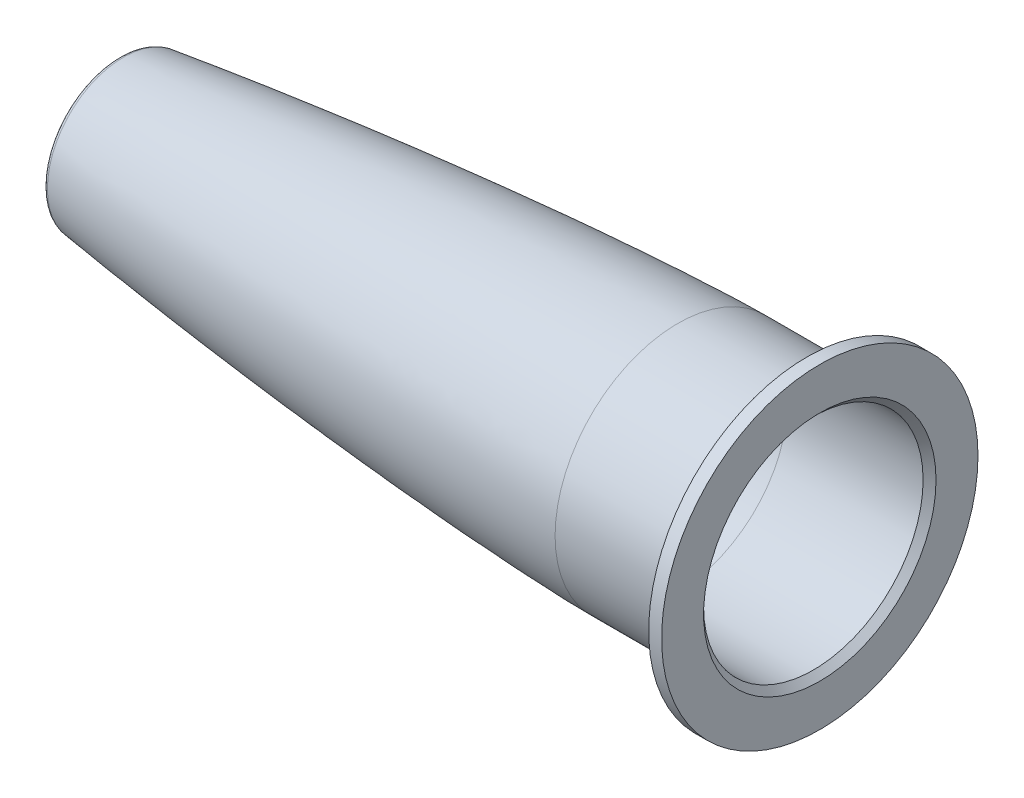
SolidWorks part; units mm, degrees
ref_plane "Front Plane" through (0, 0, 0) normal (0, 0, 1) x (1, 0, 0)
ref_plane "Top Plane" through (0, 0, 0) normal (0, 1, 0) x (1, 0, 0)
ref_plane "Right Plane" through (0, 0, 0) normal (1, 0, 0) x (0, 0, -1)
curve "Curve1"
  spline degree 3 poles (0, 0, 0) (0.3239, 0.2563, 0) (0.9404, 0.7441, 0) (1.9928, 1.2129, 0) (2.9928, 1.6503, 0) (3.9962, 2.0429, 0) (4.997, 2.4136, 0) (5.9977, 2.765, 0) (6.9982, 3.102, 0) (7.9985, 3.4266, 0) (8.9987, 3.7409, 0) (9.9989, 4.0463, 0) (10.999, 4.3437, 0) (11.9992, 4.6341, 0) (12.9993, 4.9182, 0) (13.9993, 5.1965, 0) (14.9994, 5.4695, 0) (15.9994, 5.7378, 0) (16.9995, 6.0015, 0) (17.9995, 6.261, 0) (18.9996, 6.5167, 0) (19.9996, 6.7687, 0) (20.9996, 7.0173, 0) (21.9996, 7.2626, 0) (22.9997, 7.5048, 0) (23.9997, 7.7441, 0) (24.9997, 7.9806, 0) (25.9997, 8.2145, 0) (26.9997, 8.4458, 0) (27.9997, 8.6747, 0) (28.9998, 8.9012, 0) (29.9998, 9.1256, 0) (30.9998, 9.3477, 0) (31.9998, 9.5678, 0) (32.9998, 9.7859, 0) (33.9998, 10.0021, 0) (34.9998, 10.2164, 0) (35.9998, 10.4289, 0) (36.9998, 10.6396, 0) (37.9998, 10.8486, 0) (38.9998, 11.056, 0) (39.9998, 11.2617, 0) (40.9999, 11.4659, 0) (41.9999, 11.6686, 0) (42.9999, 11.8698, 0) (43.9999, 12.0696, 0) (44.9999, 12.2679, 0) (45.9999, 12.4649, 0) (46.9999, 12.6605, 0) (47.9999, 12.8548, 0) (48.9999, 13.0478, 0) (49.9999, 13.2396, 0) (50.9999, 13.4301, 0) (51.9999, 13.6194, 0) (52.9999, 13.8076, 0) (53.9999, 13.9946, 0) (54.9999, 14.1804, 0) (55.9999, 14.3652, 0) (56.9999, 14.5488, 0) (57.9999, 14.7314, 0) (58.9999, 14.9129, 0) (59.9999, 15.0934, 0) (60.9999, 15.2728, 0) (61.9999, 15.4513, 0) (62.9999, 15.6288, 0) (63.9999, 15.8052, 0) (64.9999, 15.9808, 0) (65.9999, 16.1554, 0) (66.9999, 16.329, 0) (67.9999, 16.5018, 0) (68.9999, 16.6736, 0) (69.9999, 16.8445, 0) (70.9999, 17.0146, 0) (71.9999, 17.1838, 0) (72.9999, 17.3522, 0) (73.9999, 17.5197, 0) (74.9999, 17.6863, 0) (75.9999, 17.8522, 0) (76.9999, 18.0172, 0) (77.9999, 18.1814, 0) (78.9999, 18.3449, 0) (79.9999, 18.5075, 0) (80.9999, 18.6694, 0) (81.9999, 18.8305, 0) (82.9999, 18.9908, 0) (83.9999, 19.1504, 0) (84.9999, 19.3092, 0) (85.9999, 19.4673, 0) (86.9999, 19.6247, 0) (87.9999, 19.7814, 0) (88.9999, 19.9373, 0) (89.9999, 20.0925, 0) (90.9999, 20.2471, 0) (91.9999, 20.4009, 0) (92.9999, 20.554, 0) (93.9999, 20.7065, 0) (95, 20.8583, 0) (96, 21.0094, 0) (97, 21.1598, 0) (98, 21.3096, 0) (99, 21.4587, 0) (100, 21.6072, 0) (101, 21.755, 0) (102, 21.9022, 0) (103, 22.0488, 0) (104, 22.1947, 0) (105, 22.34, 0) (106, 22.4846, 0) (107, 22.6287, 0) (108, 22.7721, 0) (109, 22.915, 0) (110, 23.0572, 0) (111, 23.1988, 0) (112, 23.3398, 0) (113, 23.4803, 0) (114, 23.6201, 0) (115, 23.7594, 0) (116, 23.898, 0) (117, 24.0361, 0) (118, 24.1736, 0) (119, 24.3106, 0) (120, 24.4469, 0) (121, 24.5827, 0) (122, 24.718, 0) (123, 24.8526, 0) (124, 24.9867, 0) (125, 25.1203, 0) (126, 25.2533, 0) (127, 25.3857, 0) (128, 25.5176, 0) (129, 25.649, 0) (130, 25.7798, 0) (131, 25.91, 0) (132, 26.0397, 0) (133, 26.1689, 0) (134, 26.2975, 0) (135, 26.4257, 0) (136, 26.5532, 0) (137, 26.6803, 0) (138, 26.8068, 0) (139, 26.9328, 0) (140, 27.0582, 0) (141, 27.1832, 0) (142, 27.3076, 0) (143, 27.4315, 0) (144, 27.5549, 0) (145, 27.6777, 0) (146, 27.8001, 0) (147, 27.9219, 0) (148, 28.0432, 0) (149, 28.1641, 0) (150, 28.2844, 0) (151, 28.4041, 0) (152, 28.5234, 0) (153, 28.6422, 0) (154, 28.7605, 0) (155, 28.8782, 0) (156, 28.9955, 0) (157, 29.1122, 0) (158, 29.2285, 0) (159, 29.3442, 0) (160, 29.4595, 0) (161, 29.5742, 0) (162, 29.6885, 0) (163, 29.8022, 0) (164, 29.9155, 0) (165, 30.0282, 0) (166, 30.1405, 0) (167, 30.2522, 0) (168, 30.3635, 0) (169, 30.4743, 0) (170, 30.5845, 0) (171, 30.6943, 0) (172, 30.8036, 0) (173, 30.9124, 0) (174, 31.0207, 0) (175, 31.1285, 0) (176, 31.2358, 0) (177, 31.3426, 0) (178, 31.4489, 0) (179, 31.5547, 0) (180, 31.66, 0) (181, 31.7649, 0) (182, 31.8692, 0) (183, 31.973, 0) (184, 32.0764, 0) (185, 32.1792, 0) (186, 32.2816, 0) (187, 32.3834, 0) (188, 32.4848, 0) (189, 32.5856, 0) (190, 32.686, 0) (191, 32.7859, 0) (192, 32.8852, 0) (193, 32.9841, 0) (194, 33.0825, 0) (195, 33.1803, 0) (196, 33.2777, 0) (197, 33.3746, 0) (198, 33.4709, 0) (199, 33.5668, 0) (200, 33.6621, 0) (201, 33.757, 0) (202, 33.8513, 0) (203, 33.9451, 0) (204, 34.0385, 0) (205, 34.1313, 0) (206, 34.2236, 0) (207, 34.3153, 0) (208, 34.4066, 0) (209, 34.4973, 0) (210, 34.5876, 0) (211, 34.6773, 0) (212, 34.7665, 0) (213, 34.8551, 0) (214, 34.9433, 0) (215, 35.0309, 0) (216, 35.118, 0) (217, 35.2045, 0) (218, 35.2906, 0) (219, 35.3761, 0) (220, 35.461, 0) (221, 35.5454, 0) (222, 35.6293, 0) (223, 35.7126, 0) (224, 35.7954, 0) (225, 35.8776, 0) (226, 35.9593, 0) (227, 36.0404, 0) (228, 36.121, 0) (229, 36.201, 0) (230, 36.2805, 0) (231, 36.3594, 0) (232, 36.4377, 0) (233, 36.5154, 0) (234, 36.5926, 0) (235, 36.6692, 0) (236, 36.7452, 0) (237, 36.8206, 0) (238, 36.8954, 0) (239, 36.9696, 0) (240, 37.0432, 0) (241, 37.1163, 0) (242, 37.1887, 0) (243, 37.2605, 0) (244, 37.3317, 0) (245, 37.4022, 0) (246, 37.4722, 0) (247, 37.5415, 0) (248, 37.6102, 0) (249, 37.6782, 0) (250, 37.7455, 0) (251, 37.8123, 0) (252, 37.8783, 0) (253, 37.9437, 0) (254, 38.0084, 0) (255, 38.0725, 0) (256, 38.1358, 0) (257, 38.1985, 0) (258, 38.2604, 0) (259, 38.3216, 0) (260, 38.3821, 0) (261, 38.4419, 0) (262, 38.5009, 0) (263, 38.5592, 0) (264, 38.6168, 0) (265, 38.6735, 0) (266, 38.7295, 0) (267, 38.7847, 0) (268, 38.8391, 0) (269, 38.8926, 0) (270, 38.9454, 0) (271, 38.9972, 0) (272, 39.0483, 0) (273, 39.0984, 0) (274, 39.1477, 0) (275, 39.196, 0) (276, 39.2434, 0) (277, 39.2899, 0) (278, 39.3354, 0) (279, 39.3799, 0) (280, 39.4234, 0) (281, 39.4658, 0) (282, 39.5072, 0) (283, 39.5475, 0) (284, 39.5866, 0) (285, 39.6246, 0) (286, 39.6613, 0) (287, 39.6968, 0) (288, 39.731, 0) (289, 39.7638, 0) (290, 39.7952, 0) (291, 39.8251, 0) (292, 39.8533, 0) (293, 39.88, 0) (294, 39.9048, 0) (295, 39.9276, 0) (296, 39.9483, 0) (297, 39.9666, 0) (298, 39.982, 0) (299, 39.9947, 0) (299.6667, 39.9982, 0) (300, 40, 0) knots 0 0 0 0 0.004064 0.007736 0.011323 0.014865 0.018378 0.021871 0.025347 0.028811 0.032264 0.035709 0.039146 0.042576 0.046001 0.04942 0.052835 0.056246 0.059653 0.063056 0.066457 0.069854 0.073248 0.07664 0.08003 0.083417 0.086802 0.090186 0.093567 0.096946 0.100324 0.1037 0.107075 0.110448 0.11382 0.11719 0.120559 0.123927 0.127294 0.130659 0.134023 0.137387 0.140749 0.14411 0.14747 0.15083 0.154188 0.157546 0.160902 0.164258 0.167613 0.170968 0.174321 0.177674 0.181026 0.184378 0.187728 0.191078 0.194428 0.197776 0.201124 0.204472 0.207819 0.211165 0.214511 0.217856 0.221201 0.224545 0.227888 0.231231 0.234574 0.237916 0.241258 0.244599 0.247939 0.251279 0.254619 0.257958 0.261297 0.264636 0.267974 0.271311 0.274648 0.277985 0.281321 0.284657 0.287993 0.291328 0.294663 0.297997 0.301331 0.304665 0.307999 0.311332 0.314664 0.317997 0.321329 0.32466 0.327992 0.331323 0.334653 0.337984 0.341314 0.344643 0.347973 0.351302 0.354631 0.35796 0.361288 0.364616 0.367943 0.371271 0.374598 0.377925 0.381251 0.384578 0.387904 0.39123 0.394555 0.39788 0.401205 0.40453 0.407855 0.411179 0.414503 0.417827 0.42115 0.424474 0.427797 0.431119 0.434442 0.437764 0.441086 0.444408 0.44773 0.451051 0.454372 0.457693 0.461014 0.464335 0.467655 0.470975 0.474295 0.477615 0.480934 0.484253 0.487572 0.490891 0.49421 0.497528 0.500846 0.504165 0.507482 0.5108 0.514117 0.517435 0.520752 0.524068 0.527385 0.530702 0.534018 0.537334 0.54065 0.543965 0.547281 0.550596 0.553911 0.557226 0.560541 0.563856 0.56717 0.570484 0.573799 0.577112 0.580426 0.58374 0.587053 0.590366 0.593679 0.596992 0.600305 0.603617 0.606929 0.610242 0.613554 0.616865 0.620177 0.623489 0.6268 0.630111 0.633422 0.636733 0.640043 0.643354 0.646664 0.649974 0.653284 0.656594 0.659904 0.663213 0.666523 0.669832 0.673141 0.67645 0.679759 0.683067 0.686376 0.689684 0.692992 0.6963 0.699608 0.702916 0.706223 0.70953 0.712838 0.716145 0.719452 0.722758 0.726065 0.729371 0.732678 0.735984 0.73929 0.742596 0.745901 0.749207 0.752512 0.755817 0.759122 0.762427 0.765732 0.769037 0.772341 0.775646 0.77895 0.782254 0.785558 0.788862 0.792165 0.795469 0.798772 0.802075 0.805378 0.808681 0.811984 0.815287 0.818589 0.821891 0.825193 0.828496 0.831797 0.835099 0.838401 0.841702 0.845003 0.848305 0.851606 0.854907 0.858207 0.861508 0.864808 0.868109 0.871409 0.874709 0.878009 0.881308 0.884608 0.887907 0.891207 0.894506 0.897805 0.901104 0.904402 0.907701 0.910999 0.914297 0.917596 0.920894 0.924191 0.927489 0.930787 0.934084 0.937381 0.940678 0.943975 0.947272 0.950569 0.953865 0.957161 0.960458 0.963754 0.96705 0.970345 0.973641 0.976936 0.980232 0.983527 0.986822 0.990117 0.993411 0.996706 1 1 1 1
sketch "Sketch2" plane through (0, 0, 0) normal (0, 0, 1) x (1, 0, 0)
  line L0 (0, 0) -> (125, 0) construction
  line L2 (300, 40) -> (300.0106, 38) construction
  line L3 (0, 0) -> (4.2671, 0)
  line L4 (300, 40) -> (340, 40)
  line L5 (340, 40) -> (340, 38)
  line L6 (340, 38) -> (300.0106, 38)
  line L7 (125, 25.1202) -> (125, 23.1025)
  line L8 (125, 0) -> (127, 0) construction
  line L9 (127, 0) -> (127, 23.3682)
  line L10 (340, 38) -> (340, 34)
  line L11 (340, 34) -> (300.0106, 34)
  line L12 (127, 0) -> (131, 0)
  line L13 (131, 0) -> (131, 20)
  line L14 (127, 0) -> (131, 0)
  line L15 (125, 0) -> (127, 0) construction
  line L16 (127, 0) -> (1129.646, 0) construction
  line L17 (125, 23.1025) -> (125, 0) construction
  arc A0 (300.0106, 34) -> (131, 20) centre (348.2024, -1574.9403) ccw
  spline S0 degree 3 poles (-1605.8079, 2533.2499) (16.7759, -86.5021) (-13.4623, -5.6713) (1.9928, 1.2129) (2.9928, 1.6503) (3.9962, 2.0429) (4.997, 2.4136) (5.9977, 2.765) (6.9982, 3.102) (7.9985, 3.4266) (8.9987, 3.7409) (9.9989, 4.0463) (10.999, 4.3437) (11.9992, 4.6341) (12.9993, 4.9182) (13.9993, 5.1965) (14.9994, 5.4695) (15.9994, 5.7378) (17.3322, 6.0892) (18.9983, 6.5182) (20.9985, 7.0186) (22.9987, 7.506) (24.9988, 7.9817) (26.9989, 8.4468) (28.999, 8.9022) (31.332, 9.4229) (33.9983, 10.0043) (36.9985, 10.6416) (39.9986, 11.2636) (42.9987, 11.8715) (46.3318, 12.5325) (49.9982, 13.2423) (53.9984, 13.9971) (57.9985, 14.7338) (62.3316, 15.5134) (66.9981, 16.3324) (71.9982, 17.187) (77.3314, 18.0757) (82.9979, 18.9949) (88.9981, 19.9411) (95.3312, 20.913) (101.9978, 21.907) (108.9979, 22.9195) (116.3311, 23.9492) (123.9977, 24.9923) (131.9978, 26.0451) (140.331, 27.1059) (148.9975, 28.1706) (157.9977, 29.2349) (166.9978, 30.2586) (175.9979, 31.2421) (184.998, 32.1856) (193.998, 33.089) (202.665, 33.9198) (210.9985, 34.6826) (218.6654, 35.3525) (225.9989, 35.9637) (232.9989, 36.5199) (239.6657, 37.0229) (245.9992, 37.4758) (251.666, 37.8596) (256.9995, 38.2012) (261.6662, 38.4837) (265.9996, 38.7315) (269.9996, 38.9474) (273.6664, 39.1331) (276.9998, 39.2912) (279.9998, 39.4248) (282.6665, 39.5352) (284.9999, 39.6252) (286.9999, 39.6975) (288.9999, 39.7645) (290.6666, 39.8156) (292.3333, 39.8628) (293.6666, 39.8971) (295, 39.9276) (296, 39.9483) (297, 39.9666) (298, 39.982) (343.7491, 40.5639) (389.362, 18.16) (408.5654, 3036.1615) knots -0.154953 -0.154953 -0.154953 -0.154953 0.004064 0.007736 0.011323 0.014865 0.018378 0.021871 0.025347 0.028811 0.032264 0.035709 0.039146 0.042576 0.046001 0.04942 0.052835 0.056246 0.059653 0.066457 0.073248 0.08003 0.086802 0.093567 0.100324 0.107075 0.11719 0.127294 0.137387 0.14747 0.157546 0.170968 0.184378 0.197776 0.211165 0.227888 0.244599 0.261297 0.281321 0.301331 0.321329 0.344643 0.367943 0.39123 0.417827 0.444408 0.470975 0.500846 0.530702 0.560541 0.590366 0.620177 0.649974 0.679759 0.706223 0.732678 0.755817 0.77895 0.802075 0.821891 0.841702 0.858207 0.874709 0.887907 0.901104 0.914297 0.924191 0.934084 0.943975 0.950569 0.957161 0.963754 0.970345 0.973641 0.980232 0.983527 0.986822 0.990117 0.993411 0.996706 1.44228 1.44228 1.44228 1.44228 only from (0, 0) to (300, 40) construction
  spline S1 degree 3 poles (125, 25.1202) (128.3322, 25.5643) (134.6636, 26.3906) (143.9975, 27.5615) (152.9976, 28.6487) (161.9977, 29.6949) (170.9978, 30.7007) (179.9979, 31.6664) (188.998, 32.5921) (197.6649, 33.4447) (205.9985, 34.2288) (213.9985, 34.9487) (221.6654, 35.6063) (228.9989, 36.2054) (235.6657, 36.7239) (241.9992, 37.1922) (247.9992, 37.6138) (253.666, 37.9902) (258.9995, 38.3245) (263.6662, 38.6001) (267.9996, 38.8411) (271.9996, 39.0504) (275.6664, 39.2295) (278.9998, 39.3813) (281.9998, 39.5087) (284.6665, 39.6131) (286.9999, 39.6975) (288.9999, 39.7645) (290.6666, 39.8156) (292.3333, 39.8628) (293.6666, 39.8971) (295, 39.9276) (296, 39.9483) (297, 39.9666) (298, 39.982) (299, 39.9947) (299.6667, 39.9982) (300, 40) knots 0.42115 0.42115 0.42115 0.42115 0.454372 0.484253 0.514117 0.543965 0.573799 0.603617 0.633422 0.663213 0.689684 0.716145 0.742596 0.765732 0.788862 0.808681 0.828496 0.848305 0.864808 0.881308 0.894506 0.907701 0.920894 0.930787 0.940678 0.950569 0.957161 0.963754 0.970345 0.973641 0.980232 0.983527 0.986822 0.990117 0.993411 0.996706 1 1 1 1 construction
  spline S2 degree 1 poles (125.2642, 23.1377) (300.0106, 38) knots 0 0 1 1 construction
  spline S3 degree 3 poles (125.2642, 23.1377) (125.6981, 23.1956) (126.4214, 23.2917) (140.9222, 25.2103) (169.5342, 28.6684) (205.201, 32.2375) (234.3548, 34.6602) (256.2397, 36.2005) (274.4836, 37.2162) (289.0918, 37.7888) (296.3679, 37.9808) (300.0106, 38) knots 0.42115 0.42115 0.42115 0.42115 0.425481 0.428368 0.565863 0.710575 0.782931 0.855288 0.927644 0.963822 1 1 1 1 only from (127, 23.3682) to (300.0106, 38)
  spline S4 degree 3 poles (0, 0) (0.3239, 0.2563) (0.9404, 0.7441) (1.9928, 1.2129) (2.9928, 1.6503) (3.9962, 2.0429) (4.997, 2.4136) (5.9977, 2.765) (6.9982, 3.102) (7.9985, 3.4266) (8.9987, 3.7409) (9.9989, 4.0463) (10.999, 4.3437) (11.9992, 4.6341) (12.9993, 4.9182) (13.9993, 5.1965) (14.9994, 5.4695) (15.9994, 5.7378) (17.3322, 6.0892) (18.9983, 6.5182) (20.9985, 7.0186) (22.9987, 7.506) (24.9988, 7.9817) (26.9989, 8.4468) (28.999, 8.9022) (31.332, 9.4229) (33.9983, 10.0043) (36.9985, 10.6416) (39.9986, 11.2636) (42.9987, 11.8715) (46.3318, 12.5325) (49.9982, 13.2423) (53.9984, 13.9971) (57.9985, 14.7338) (62.3316, 15.5134) (66.9981, 16.3324) (71.9982, 17.187) (77.3314, 18.0757) (82.9979, 18.9949) (88.9981, 19.9411) (95.3312, 20.913) (101.9978, 21.907) (108.9979, 22.9195) (116.3311, 23.9492) (121.6658, 24.675) (124.6667, 25.0758) (125, 25.1202) knots 0 0 0 0 0.004064 0.007736 0.011323 0.014865 0.018378 0.021871 0.025347 0.028811 0.032264 0.035709 0.039146 0.042576 0.046001 0.04942 0.052835 0.056246 0.059653 0.066457 0.073248 0.08003 0.086802 0.093567 0.100324 0.107075 0.11719 0.127294 0.137387 0.14747 0.157546 0.170968 0.184378 0.197776 0.211165 0.227888 0.244599 0.261297 0.281321 0.301331 0.321329 0.344643 0.367943 0.39123 0.417827 0.42115 0.42115 0.42115 0.42115 construction
  spline S5 degree 3 poles (4.2671, 0) (4.3107, 0.0171) (4.5258, 0.1012) (5.4558, 0.4556) (7.0834, 1.031) (10.037, 1.984) (13.7867, 3.0797) (18.3317, 4.2942) (22.9057, 5.4346) (29.0314, 6.8774) (36.7255, 8.5622) (45.9958, 10.445) (55.293, 12.2166) (64.6107, 13.8956) (77.0563, 16.0277) (92.6469, 18.5165) (108.7755, 20.885) (119.566, 22.3741) (124.1012, 22.9826) (125, 23.1025) knots 0.013225 0.013225 0.013225 0.013225 0.013714 0.015625 0.023438 0.03125 0.046875 0.0625 0.078125 0.09375 0.125 0.15625 0.1875 0.21875 0.25 0.3125 0.375 0.4113 0.420271 0.420271 0.420271 0.420271 construction
  spline S6 degree 3 poles (125, 23.1025) (125.6666, 23.1914) (126.3333, 23.28) (127, 23.3682) knots 0.420271 0.420271 0.420271 0.420271 0.426925 0.426925 0.426925 0.426925 construction
  dimension "D7" = 1609.6619
  dimension "D2" = 40
  dimension "D3" = 2
  dimension "D4" = 175
  dimension "D5" = 4
  dimension "D6" = 4
  dimension "D8" = 20
  dimension "D1" = 2
revolve "Revolve1" add sketch "Sketch2" angle 360 about L0 region at (337.8364, 36, 0)
sketch "Sketch3" plane through (125, 0, 0) normal (-1, 0, 0) x (0, 0, 1)
  circle A2 centre (0, 0) radius 3.1
  dimension "D1" = 6.2
extrude "Cut-Extrude1" cut sketch "Sketch3" against normal through all
sketch "Sketch4" plane through (340, 0, 0) normal (1, 0, 0) x (0, 0, -1)
  circle A0 centre (0, 0) radius 34
  circle A1 centre (0, 0) radius 49
  circle A2 centre (0, 0) radius 34 construction
  dimension "D1" = 15
extrude "Boss-Extrude1" add sketch "Sketch4" along normal blind 4
chamfer "Chamfer1" distance 2 angle 45 1 edges at (344, 0, -34)
sketch "Sketch5" plane through (127, 0, 0) normal (-1, 0, 0) x (0, 0, 1)
  line L0 (0, 15) -> (0, -15) construction
  line L1 (15, 0) -> (-15, 0) construction
  circle A0 centre (0, 15) radius 1.5
  circle A1 centre (15, 0) radius 1.5
  circle A2 centre (-15, 0) radius 1.5
  circle A3 centre (0, -15) radius 1.5
  dimension "D1" = 3
  dimension "D2" = 30
extrude "Boss-Extrude2" add sketch "Sketch5" along normal blind 2
chamfer "Chamfer2" distance 1 angle 60 4 edges at (125, 0, 16.5) (125, 15, 1.5) (125, 0, -13.5) (125, -15, 1.5) first distance on face at (125, 0, 16.5) first distance on face at (125, 15, 1.5) first distance on face at (125, 0, -13.5) first distance on face at (125, -15, 1.5)
fillet "Fillet1" radius 5 4 edges at (127, 15, 1.5) (127, 0, -13.5) (127, 0, 16.5) (127, -15, 1.5)
fillet "Fillet2" radius 1.5 4 edges at (126.7321, 0, -13.5) (126.7321, 15, 1.5) (126.7321, -15, 1.5) (126.7321, 0, 16.5)
fillet "Fillet3" radius 1.5 1 edges at (127, 0, 23.3682)
sketch "Sketch6" plane through (340, 0, 0) normal (-1, 0, 0) x (0, 0, 1)
  circle A0 centre (0, 0) radius 44.25
  circle A1 centre (0, 0) radius 46.25
  dimension "D1" = 88.5
  dimension "D2" = 2
extrude "Boss-Extrude3" add sketch "Sketch6" along normal blind 2
chamfer "Chamfer3" distance 0.5 angle 45 2 edges at (338, 0, 46.25) (338, 0, 44.25)
sketch "Sketch7" plane through (127, 0, 0) normal (-1, 0, 0) x (0, 0, 1)
  circle A0 centre (0, 0) radius 3.1 construction
  circle A1 centre (0, 0) radius 3.1
  circle A2 centre (0, 0) radius 5.1
  dimension "D1" = 2
extrude "Boss-Extrude4" add sketch "Sketch7" along normal blind 2
chamfer "Chamfer4" distance 1.25 angle 60 1 edges at (125, 0, 5.1) first distance on face at (125, 0, 5.1)
